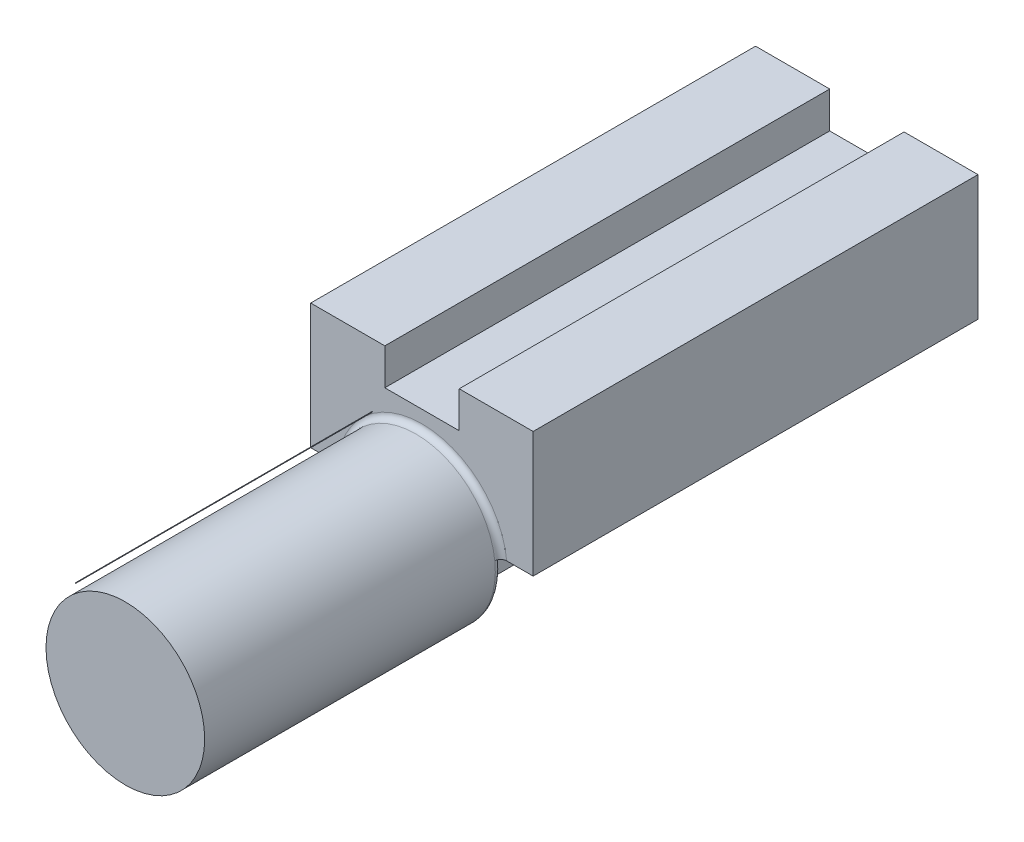
SolidWorks part; units mm, degrees
ref_plane "Front Plane" through (0, 0, 0) normal (0, 0, 1) x (1, 0, 0)
ref_plane "Top Plane" through (0, 0, 0) normal (0, 1, 0) x (1, 0, 0)
ref_plane "Right Plane" through (0, 0, 0) normal (1, 0, 0) x (0, 0, -1)
sketch "Sketch1" plane through (0, 0, 0) normal (0, 0, 1) x (1, 0, 0)
  line L1 (-47.3964, -5.6388) -> (-9.2964, -5.6388)
  line L2 (-47.3964, -5.6388) -> (-47.3964, 9.6012)
  line L3 (-34.6964, 9.6012) -> (-21.9556, 9.6012)
  line L4 (-9.2964, -5.6388) -> (-9.2964, 9.6012)
  line L6 (-47.3964, 9.6012) -> (-47.3964, 15.8242)
  line L7 (-47.3964, 15.8242) -> (-34.6964, 15.8242)
  line L8 (-34.6964, 9.6012) -> (-34.6964, 15.8242)
  line L10 (-9.2964, 9.6012) -> (-9.2964, 15.8242)
  line L11 (-9.2964, 15.8242) -> (-21.9556, 15.8242)
  line L12 (-21.9556, 9.6012) -> (-21.9556, 15.8242)
  dimension "D1" = 15.24
  dimension "D2" = 38.1
  dimension "D3" = 6.223
  dimension "D4" = 12.7
  dimension "D5" = 12.6592
extrude "Boss-Extrude1" add sketch "Sketch1" along normal blind 76.2
sketch "Sketch2" plane through (0, 0, 76.2) normal (0, 0, 1) x (1, 0, 0)
  line L1 (-47.3964, -5.6388) -> (-9.2964, -5.6388) construction
  line L4 (-41.0464, -5.6388) -> (-15.6464, -5.6388)
  line L5 (-41.0464, -5.6388) -> (-41.0464, -8.6868)
  line L6 (-41.0464, -8.6868) -> (-15.6464, -8.6868)
  line L7 (-15.6464, -5.6388) -> (-15.6464, -8.6868)
  dimension "D1" = 25.4
  dimension "D2" = 3.048
extrude "Boss-Extrude2" add sketch "Sketch2" against normal blind 38.1 separate body
sketch "Sketch4" plane through (0, 0, 76.2) normal (0, 0, 1) x (1, 0, 0)
  circle A1 centre (-36.8665, 4.9474) radius 0.0431
  circle A2 centre (-28.3464, -7.1628) radius 13.589
  dimension "D3" = 27.178
extrude "Boss-Extrude3" add sketch "Sketch4" along normal blind 50.8
fillet "Fillet2" radius 1.016 1 edges at (-28.3464, -20.7518, 76.2)
fillet "Fillet3" radius 1.016 1 edges at (-28.3464, 6.4262, 76.2)
equation "\"da\" = 2 * ( ( 4 * 0.12 ) / ( pi ) ) ^ ( 1 / 3 )"
equation "\"fillet\"= 0.04in"
equation "\"te\"= 0.245"
equation "\"La\"= 2in"
equation "\"Wb\"= 1in"
equation "\"Lb\"= 1.5in"
equation "\"tb\"= 0.12in"
equation "\"Lc\"= 3in"
equation "\"bc\"= 1.5in"
equation "\"hc\"= 0.6in"
equation "\"td\"= 0.04"
equation "\"Le\"= 0.5in"
equation "\"be\"= 1.5in"
equation "\"wd\"= 1.5in"
